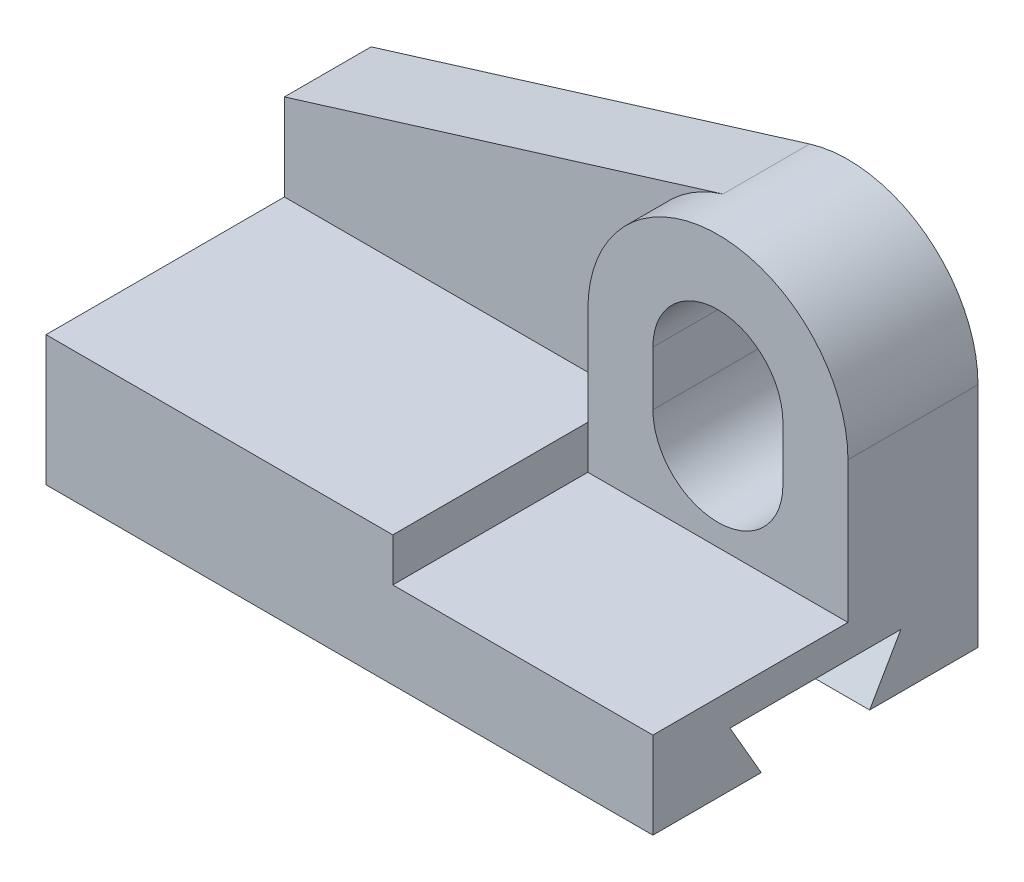
SolidWorks part; units mm, degrees
ref_plane "前视基准面" through (0, 0, 0) normal (0, 0, 1) x (1, 0, 0)
ref_plane "上视基准面" through (0, 0, 0) normal (0, 1, 0) x (1, 0, 0)
ref_plane "右视基准面" through (0, 0, 0) normal (1, 0, 0) x (0, 0, -1)
other "Configuration Table"
sketch "草图1" plane through (0, 0, 0) normal (0, 0, 1) x (1, 0, 0)
  line L0 (16.4072, 11) -> (16.4072, 6) construction
  line L1 (28.4072, -10) -> (-27.5928, -10)
  line L2 (28.4072, -10) -> (28.4072, 11)
  line L4 (-27.5928, -10) -> (-27.5928, 10)
  line L5 (22.4072, 11) -> (22.4072, 6)
  line L6 (10.4072, 11) -> (10.4072, 6)
  line L7 (-27.5928, 10) -> (12.8738, 22.468)
  line L8 (28.4072, 11) -> (10.4072, 11) construction
  line L9 (16.4072, 11) -> (16.4072, 23) construction
  line L10 (4.4072, 11) -> (4.4072, -2)
  line L11 (4.4072, -2) -> (28.4072, -2)
  line L12 (4.4072, 2) -> (-27.5928, 2)
  arc A0 (28.4072, 11) -> (12.8738, 22.468) centre (16.4072, 11) ccw
  arc A1 (22.4072, 11) -> (10.4072, 11) centre (16.4072, 11) ccw
  arc A2 (10.4072, 6) -> (22.4072, 6) centre (16.4072, 6) ccw
  arc A3 (12.8738, 22.468) -> (4.4072, 11) centre (16.4072, 11) ccw
  point P0 (0, 0)
  point P6 (23.5346, 20.654)
  point P9 (16.4072, 8.5)
  point P20 (4.4072, 11)
  dimension "D5" = 6
  dimension "D7" = 12
  dimension "D1" = 20
  dimension "D2" = 56
  dimension "D3" = 21
  dimension "D4" = 12
  dimension "D6" = 5
  dimension "D8" = 13
  dimension "D9" = 12
extrude "凸台-拉伸1" add sketch "草图1" against normal blind 8 contours A3 L7 L4 L12 L10 | L10 L12 L4 L1 L2 L11 | A0 A3 L10 L11 L2 A2 L6 A1 L5 region at (-2.2595, -4.6667, 0) region at (16.4072, -1.6534, 0) region at (-9.0166, 9.113, 0)
extrude "凸台-拉伸2" add sketch "草图1<3>" along normal blind 4 contours A0 A3 L10 L11 L2 A2 L6 A1 L5 region at (16.4072, -1.6534, 0)
sketch "草图1<3>" plane through (0, 0, 0) normal (0, 0, 1) x (1, 0, 0) same geometry as "草图1"
extrude "凸台-拉伸3" add sketch "草图1<4>" along normal blind 22 contours L10 L12 L4 L1 L2 L11 region at (-2.2595, -4.6667, 0)
sketch "草图1<4>" plane through (0, 0, 0) normal (0, 0, 1) x (1, 0, 0) same geometry as "草图1"
sketch "草图3" plane through (-27.5928, 0, 0) normal (-1, 0, 0) x (0, 0, 1)
  line L0 (7, -8.1061) -> (7, 10.0789) construction
  line L1 (-8, -10) -> (-8, 10) construction
  line L2 (2, -10) -> (-0.8868, -5)
  line L3 (-8, -10) -> (22, -10) construction
  line L4 (-0.8868, -5) -> (14.8868, -5)
  line L5 (22, -10) -> (22, 2) construction
  line L6 (12, -10) -> (14.8868, -5)
  line L7 (2, -10) -> (12, -10)
  point P13 (7, -5)
  dimension "D1" = 5
  dimension "D2" = 5
  dimension "D3" = 60
extrude "切除-拉伸1" cut sketch "草图3" against normal through all both and the other way through all
